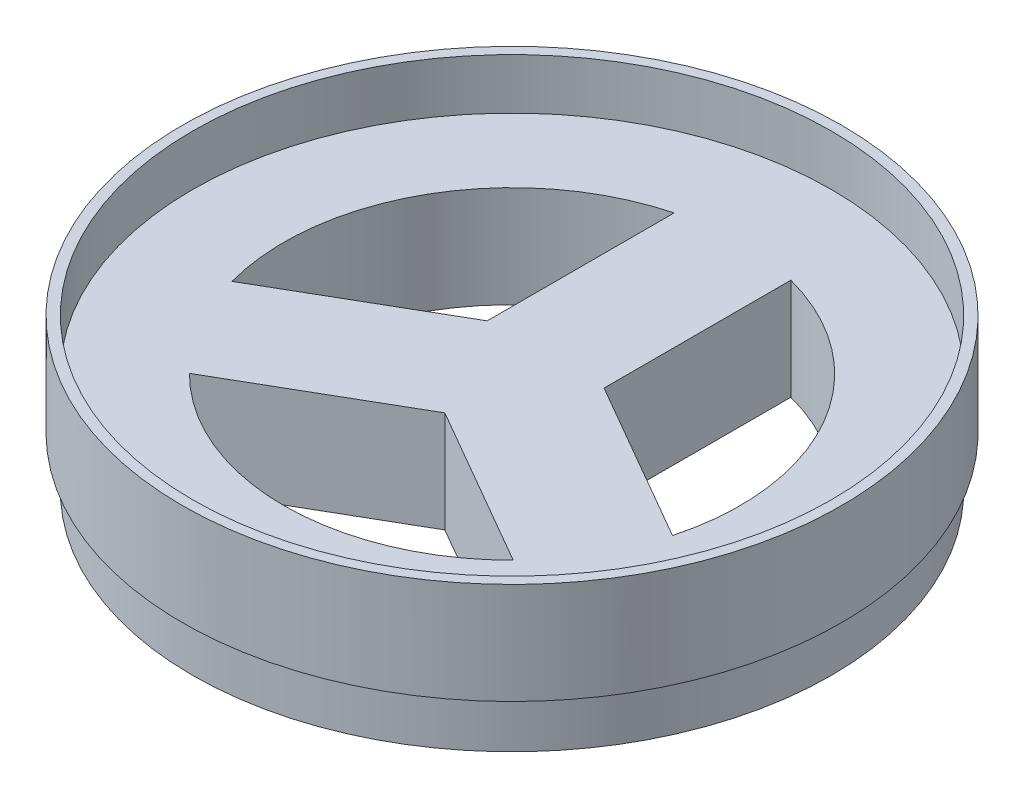
SolidWorks part; units mm, degrees
material "HYPALON"
ref_plane "Front Plane" through (0, 0, 0) normal (0, 0, 1) x (1, 0, 0)
ref_plane "Top Plane" through (0, 0, 0) normal (0, 1, 0) x (1, 0, 0)
ref_plane "Right Plane" through (0, 0, 0) normal (1, 0, 0) x (0, 0, -1)
sketch "Szkic1" plane through (0, 0, 0) normal (0, 1, 0) x (1, 0, 0)
  line L5 (0.0278, -13.2791) -> (31.9372, -31.702)
  line L6 (-11.5139, 6.6155) -> (-11.5139, 43.5021)
  line L7 (11.4861, 6.6636) -> (11.4861, 43.5094)
  line L8 (11.4861, 6.6636) -> (43.4308, -11.7797)
  line L9 (-11.5139, 6.6155) -> (-43.4233, -11.8074)
  line L10 (0.0278, -13.2791) -> (-31.917, -31.7224)
  circle A0 centre (0, 0) radius 65
  circle A1 centre (0, 0) radius 45
  point P22 (0, 0)
  dimension "D1" = 130
  dimension "D2" = 90
  dimension "D5" = 120
  dimension "D3" = 23
  dimension "D7" = 120
  dimension "D8" = 120
  dimension "D6" = 3
sketch "Szkic2" plane through (0, 0, 0) normal (0, 1, 0) x (1, 0, 0)
  circle A0 centre (0, 0) radius 35
  circle A1 centre (0, 0) radius 64
  dimension "D1" = 128
  dimension "D2" = 70
extrude "Dodanie-wyciągnięcie1" add sketch "Szkic1" along normal blind 20 contours L5 A1 L8 L7 L6 L9 L10 | A0 A1 region at (0, 0, 0) region at (-63.1615, 0, 0)
sketch "Szkic3" plane through (0, 20, 0) normal (0, 1, 0) x (1, 0, 0)
  circle A0 centre (0, 0) radius 65
  circle A1 centre (0, 0) radius 63
  circle A2 centre (0, 0) radius 65 construction
  dimension "D1" = 2
extrude "Dodanie-wyciągnięcie2" add sketch "Szkic3" along normal blind 10 contours A0 | A1
sketch "Szkic6" plane through (0, 0, 0) normal (0, -1, 0) x (1, 0, 0)
  circle A0 centre (0, 0) radius 65
  circle A1 centre (0, 0) radius 63
  dimension "D1" = 2
  dimension "D2" = 130
extrude "Wytnij-wyciągnięcie1" cut sketch "Szkic6" against normal blind 10
